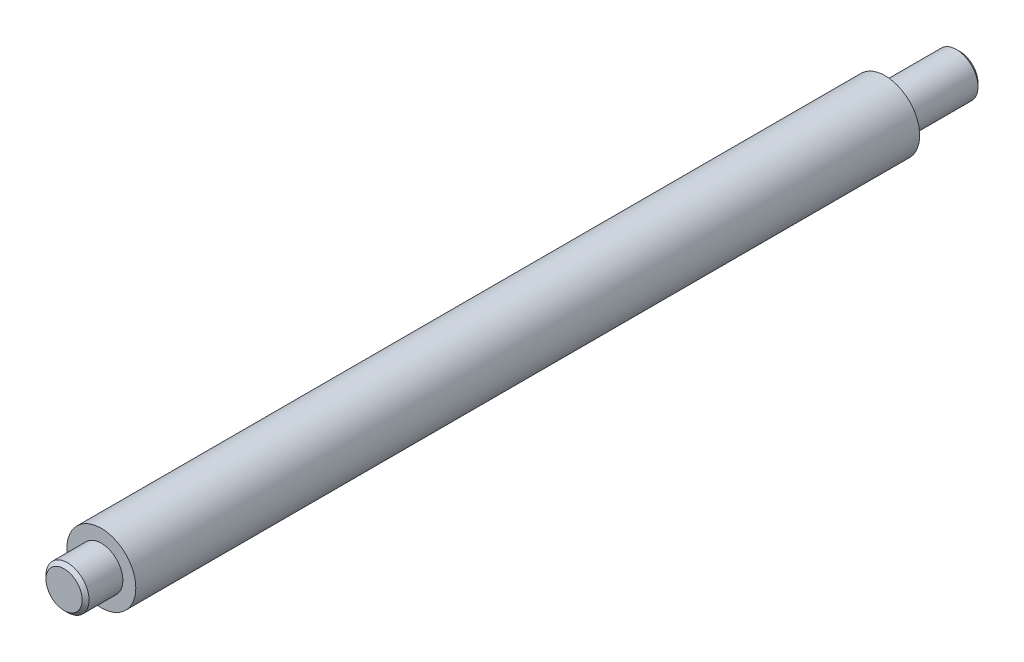
SolidWorks part; units mm, degrees
ref_plane "Front Plane" through (0, 0, 0) normal (0, 0, 1) x (1, 0, 0)
ref_plane "Top Plane" through (0, 0, 0) normal (0, 1, 0) x (1, 0, 0)
ref_plane "Right Plane" through (0, 0, 0) normal (1, 0, 0) x (0, 0, -1)
sketch "Sketch1" plane through (0, 0, 0) normal (0, 0, 1) x (1, 0, 0)
  line L2 (0, 0) -> (0, -82.7752) construction
  circle A0 centre (0, 0) radius 12.7
  dimension "D1" = 25.4
extrude "Boss-Extrude1" add sketch "Sketch1" against normal blind 330.2
ref_axis "Axis1" through (0, 0, -330.2) along (0, 0, 1)
sketch "Sketch3" plane through (0, 0, -330.2) normal (0, 0, -1) x (-1, 0, 0)
  circle A0 centre (0, 0) radius 7.9375
  circle A1 centre (0, 0) radius 12.7 construction
  circle A2 centre (0, 0) radius 12.7
  dimension "D1" = 15.875
extrude "Cut-Extrude2" cut sketch "Sketch3" against normal blind 27.5336
sketch "Sketch2" plane through (0, 0, 0) normal (0, 0, 1) x (1, 0, 0)
  circle A0 centre (0, 0) radius 7.9375
  circle A1 centre (0, 0) radius 12.7 construction
  circle A2 centre (0, 0) radius 12.7
  dimension "D1" = 15.875
extrude "Cut-Extrude1" cut sketch "Sketch2" against normal blind 13.7414
chamfer "Chamfer1" distance 1.27 angle 45 2 edges at (7.9375, 0, 0) (-7.9375, 0, -330.2)
